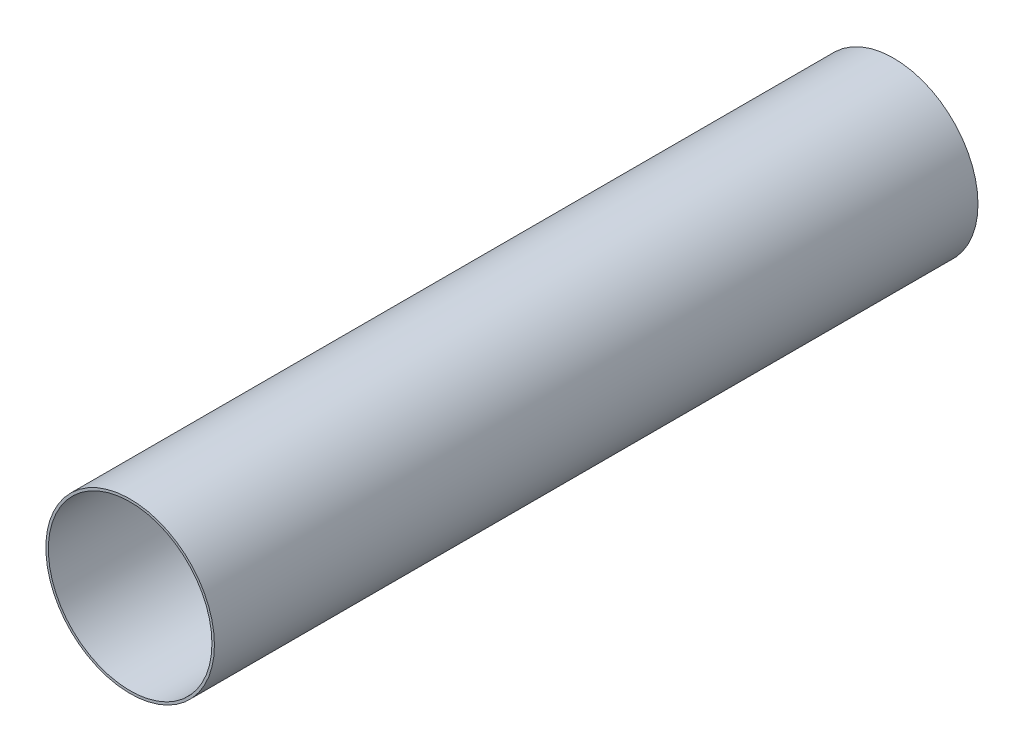
SolidWorks part; units mm, degrees
ref_plane "Front Plane" through (0, 0, 0) normal (0, 0, 1) x (1, 0, 0)
ref_plane "Top Plane" through (0, 0, 0) normal (0, 1, 0) x (1, 0, 0)
ref_plane "Right Plane" through (0, 0, 0) normal (1, 0, 0) x (0, 0, -1)
sketch "Sketch1" plane through (0, 0, 0) normal (0, 0, 1) x (1, 0, 0)
  circle A0 centre (0, 0) radius 39.2557
  circle A1 centre (0, 0) radius 38.1
  dimension "D1" = 76.2
  dimension "D2" = 78.5114
extrude "Boss-Extrude1" add sketch "Sketch1" along normal mid plane 355.6
equation "\"AIRFRAME_OD\"= 5.15in"
equation "\"AIRFRAME_ID\"= 5.00in"
equation "\"FLAT_T\"= 0.125in"
equation "\"NOSE_EXP_L\"= 27in"
equation "\"NOSE_SHOULDER_L\"= 5in"
equation "\"MAIN_L\"= 30in"
equation "\"RECO_COUP_L\"= 10in"
equation "\"RECO_SWITCH_L\"= 2in"
equation "\"DROGUE_L\"= 20in"
equation "\"ATS_FORE_COUP_L\"= 5.5in"
equation "\"ATS_AFT_COUP_L\"= 4.5in"
equation "\"LOWER_L\"= 30in"
equation "\"FIN_N\"= 4"
equation "\"CR_AFT_X\"= 0.5in"
equation "\"CR_FORE_X\"= 9.25in"
equation "\"D1@Sketch1\"=\"MOTOR_ID\""
equation "\"D2@Sketch1\"=\"MOTOR_OD\""
equation "\"D1@Boss-Extrude1\"=\"MOTOR_L\""
equation "\"FIN_ROOT\"= 8in"
equation "\"FIN_X\"= 0.75in"
equation "\"MOTOR_OD\"= 3.091in"
equation "\"MOTOR_ID\"= 3.00in"
equation "\"COUPLER_OD\"= 4.998in"
equation "\"COUPLER_ID\"= 4.88in"
equation "\"RECO_ROD_X\"= 3.5in"
equation "\"ATS_ROD_X\"= 3.75in"
equation "\"MOTOR_L\"= 14in"
equation "\"MOTOR_LOWER_X\"= 2in"
